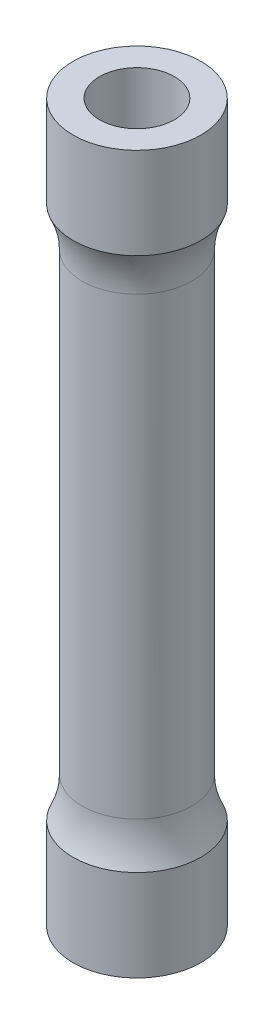
SolidWorks part; units mm, degrees
material "ABS"
ref_plane "Ön Düzlem" through (0, 0, 0) normal (0, 0, 1) x (1, 0, 0)
ref_plane "Üst Düzlem" through (0, 0, 0) normal (0, 1, 0) x (1, 0, 0)
ref_plane "Sağ Düzlem" through (0, 0, 0) normal (1, 0, 0) x (0, 0, -1)
sketch "Çizim1" plane through (0, 0, 0) normal (0, 1, 0) x (1, 0, 0)
  circle A0 centre (0, 0) radius 4.1
  circle A1 centre (0, 0) radius 6
  dimension "D1" = 8.2
  dimension "D2" = 12
extrude "Yükseklik-Ekstrüzyon1" add sketch "Çizim1" along normal blind 39.25 and the other way blind 39.25
sketch "Çizim2" plane through (0, 39.25, 0) normal (0, 1, 0) x (1, 0, 0)
  circle A0 centre (0, 0) radius 7
  circle A1 centre (0, 0) radius 4.1
  dimension "D1" = 14
extrude "Yükseklik-Ekstrüzyon2" add sketch "Çizim2" against normal blind 10
mirror "Aynalama1" about plane through (0, 0, 0) normal (0, 1, 0) of "Yükseklik-Ekstrüzyon2"
fillet "Radyus1" radius 10 2 edges at (0, -29.25, -6) (0, 29.25, 6)
